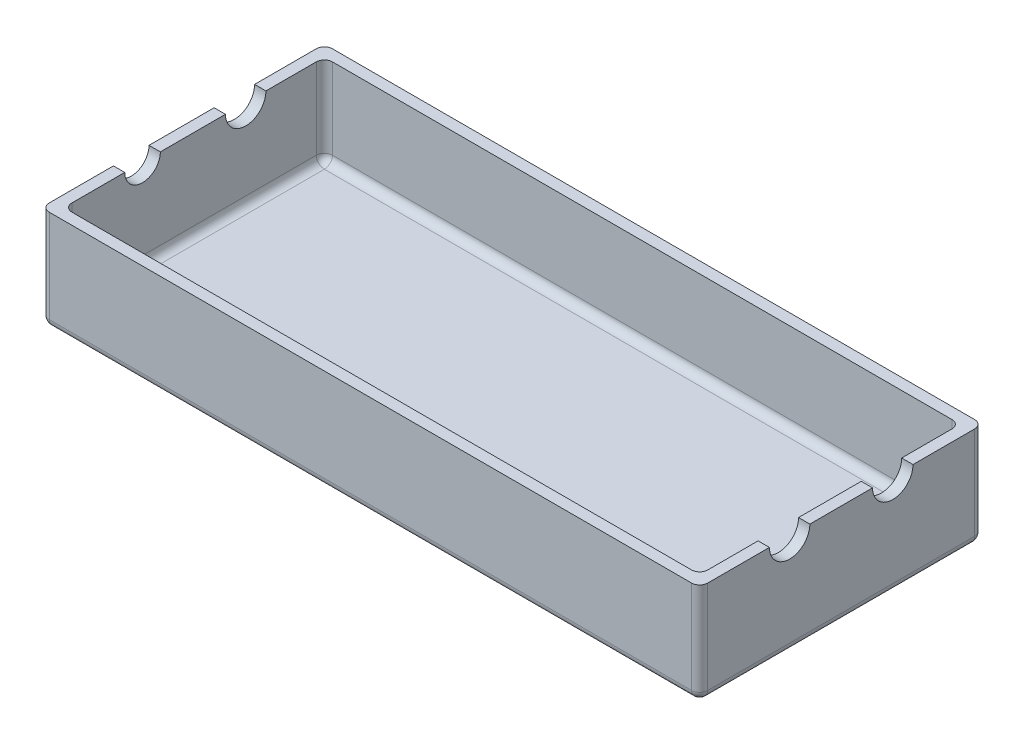
SolidWorks part; units mm, degrees
ref_plane "Front Plane" through (0, 0, 0) normal (0, 0, 1) x (1, 0, 0)
ref_plane "Top Plane" through (0, 0, 0) normal (0, 1, 0) x (1, 0, 0)
ref_plane "Right Plane" through (0, 0, 0) normal (1, 0, 0) x (0, 0, -1)
sketch "Sketch1" plane through (0, 0, 0) normal (0, 1, 0) x (1, 0, 0)
  line L1 (407, -175) -> (-407, -175)
  line L2 (407, -175) -> (407, 175)
  line L3 (407, 175) -> (-407, 175)
  line L4 (-407, -175) -> (-407, 175)
  line L5 (407, -175) -> (-407, 175) construction
  line L6 (407, 175) -> (-407, -175) construction
  line L11 (-393, -161) -> (393, 161) construction
  line L12 (-393, 161) -> (393, -161) construction
  point P0 (0, 0)
  point P6 (0, 0)
  dimension "D1" = 350
  dimension "D2" = 814
extrude "Boss-Extrude1" add sketch "Sketch1" along normal blind 125
sketch "Sketch2" plane through (0, 125, 0) normal (0, 1, 0) x (1, 0, 0)
  line L0 (-407, 175) -> (-407, -175) construction
  line L1 (-393, -161) -> (393, -161)
  line L2 (-393, -161) -> (-393, 161)
  line L3 (-393, 161) -> (393, 161)
  line L4 (393, -161) -> (393, 161)
  line L5 (-393, -161) -> (393, 161) construction
  line L6 (-393, 161) -> (393, -161) construction
  line L7 (407, 175) -> (-407, 175) construction
  point P0 (0, 0)
  dimension "D1" = 14
  dimension "D2" = 14
extrude "Cut-Extrude1" cut sketch "Sketch2" against normal blind 110
fillet "Fillet1" radius 10 4 edges at (0, 0, 175) (-407, 0, 0) (0, 0, -175) (407, 0, 0)
fillet "Fillet2" radius 10 8 edges at (-404.0711, 2.9289, -172.0711) (-404.0711, 2.9289, 172.0711) (404.0711, 2.9289, 172.0711) (404.0711, 2.9289, -172.0711) (-407, 67.5, -175) (-407, 67.5, 175) (407, 67.5, 175) (407, 67.5, -175)
fillet "Fillet3" radius 10 8 edges at (393, 70, 161) (0, 15, 161) (-393, 70, 161) (-393, 15, 0) (393, 15, 0) (0, 15, -161) (-393, 70, -161) (393, 70, -161)
ref_plane "Plane1" through (0, 0, 0) normal (0, 0, 1) x (1, 0, 0)
sketch "Sketch4" plane through (-407, 0, 0) normal (-1, 0, 0) x (0, 0, 1)
  line L0 (-63.75, 74.8846) -> (63.75, 74.8846) construction
  line L1 (0, -55) -> (0, 55) construction
  line L2 (-63.75, 74.8846) -> (-63.75, 125) construction
  line L3 (63.75, 74.8846) -> (63.75, 125) construction
  line L4 (-101.457, 125) -> (132.0433, 125) construction
  line L5 (-165, 125) -> (165, 125) construction
  circle A0 centre (-63.75, 125) radius 25
  circle A1 centre (63.75, 125) radius 22
  dimension "D3" = 50
  dimension "D4" = 44
  dimension "D1" = 63.75
  dimension "D2" = 63.75
extrude "Cut-Extrude2" cut sketch "Sketch4" against normal blind 110
sketch "Sketch5" plane through (407, 0, 0) normal (1, 0, 0) x (0, 0, -1)
  line L0 (-63.75, 75.6306) -> (63.75, 75.6306) construction
  line L1 (0, 55) -> (0, -55) construction
  line L2 (-63.75, 75.6306) -> (-63.75, 125) construction
  line L3 (63.75, 75.6306) -> (63.75, 125) construction
  line L4 (-114.8852, 125) -> (118.6152, 125) construction
  line L5 (-165, 125) -> (165, 125) construction
  circle A0 centre (-63.75, 125) radius 25
  circle A1 centre (63.75, 125) radius 25
  dimension "D3" = 50
  dimension "D4" = 50
  dimension "D1" = 63.75
  dimension "D2" = 63.75
extrude "Cut-Extrude3" cut sketch "Sketch5" against normal blind 110
